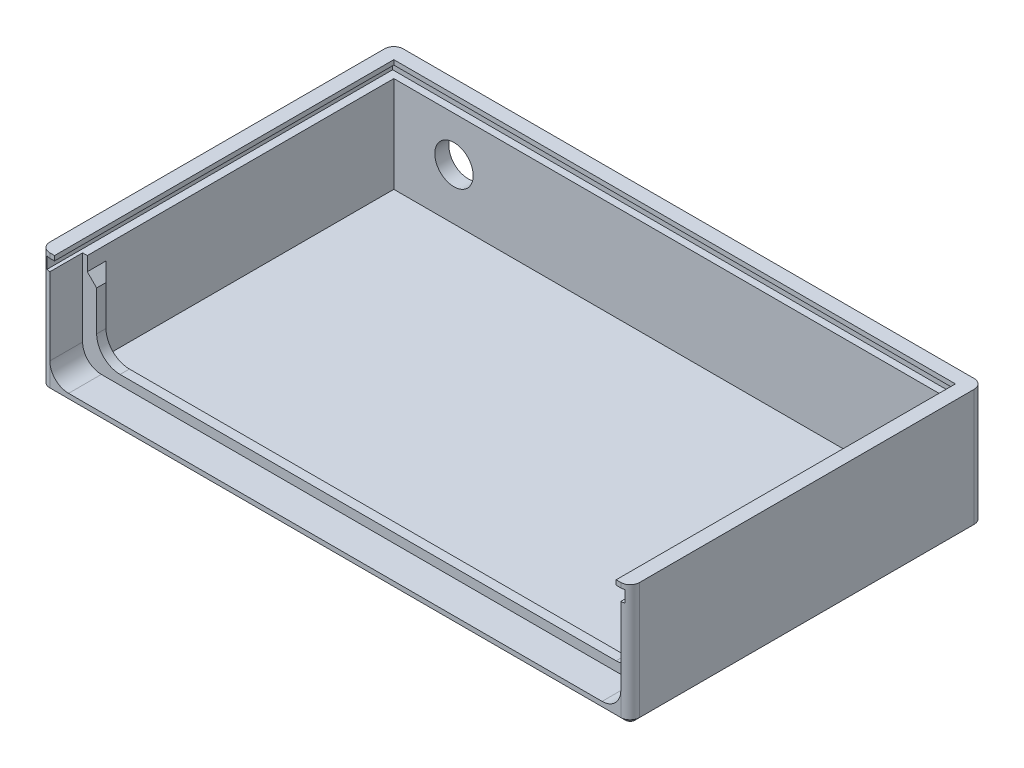
SolidWorks part; units mm, degrees
ref_plane "Plan de face" through (0, 0, 0) normal (0, 0, 1) x (1, 0, 0)
ref_plane "Plan de dessus" through (0, 0, 0) normal (0, 1, 0) x (1, 0, 0)
ref_plane "Plan de droite" through (0, 0, 0) normal (1, 0, 0) x (0, 0, -1)
sketch "Esquisse1" plane through (0, 0, 0) normal (0, 1, 0) x (1, 0, 0)
  line L1 (-63, -37.75) -> (63, -37.75)
  line L2 (-63, -37.75) -> (-63, 37.75)
  line L3 (-63, 37.75) -> (63, 37.75)
  line L4 (63, -37.75) -> (63, 37.75)
  line L5 (-63, -37.75) -> (63, 37.75) construction
  line L6 (-63, 37.75) -> (63, -37.75) construction
  point P0 (0, 0)
  dimension "D1" = 75.5
  dimension "D2" = 126
extrude "Boss.-Extru.1" add sketch "Esquisse1" along normal blind 2
sketch "Esquisse2" plane through (0, 2, 0) normal (0, 1, 0) x (1, 0, 0)
  line L0 (-63, -37.75) -> (-63, 37.75)
  line L1 (63, 37.75) -> (-63, 37.75) construction
  line L2 (-63, 37.75) -> (63, 37.75)
  line L3 (63, 37.75) -> (63, -37.75)
  line L4 (63, -37.75) -> (60, -37.75)
  line L5 (-63, -37.75) -> (63, -37.75) construction
  line L6 (60, -37.75) -> (60, 34.75)
  line L7 (60, 34.75) -> (-60, 34.75)
  line L8 (-60, 34.75) -> (-60, -37.75)
  line L9 (-60, -37.75) -> (-63, -37.75)
  line L10 (0, 34.75) -> (0, 37.75) construction
  dimension "D1" = 3
extrude "Boss.-Extru.2" add sketch "Esquisse2" along normal blind 24
ref_plane "Plan1" through (0, 25, 0) normal (0, 1, 0) x (1, 0, 0)
sketch "Esquisse3" plane through (0, 25, 0) normal (0, 1, 0) x (1, 0, 0)
  line L0 (60, -37.75) -> (63, -37.75) construction
  line L1 (-61.75, 36.25) -> (61.75, 36.25)
  line L2 (-61.75, 36.25) -> (-61.75, -37.75)
  line L3 (-61.75, -37.75) -> (61.75, -37.75)
  line L4 (61.75, 36.25) -> (61.75, -37.75)
  line L5 (-60, 34.75) -> (60, 34.75) construction
  line L6 (0, 0) -> (0, -37.75) construction
  dimension "D1" = 1.5
  dimension "D2" = 123.5
extrude "Enlèv. mat.-Extru.1" cut sketch "Esquisse3" against normal blind 2.5
sketch "Esquisse4" plane through (0, 0, 37.75) normal (0, 0, 1) x (1, 0, 0)
  line L0 (-60, 2) -> (-60, 17.5)
  line L1 (-60, 22.5) -> (-60, 2) construction
  line L2 (-60, 17.5) -> (-58, 17.5)
  line L3 (-58, 17.5) -> (-58, 9)
  line L4 (-53, 4) -> (0, 4)
  line L5 (0, 4) -> (0, 2)
  line L6 (-60, 2) -> (60, 2) construction
  line L7 (0, 2) -> (-60, 2)
  line L9 (61.75, 22.5) -> (-61.75, 22.5) construction
  arc A0 (-58, 9) -> (-53, 4) centre (-53, 9) ccw
  point P8 (-5.163, 9.9708)
  dimension "D1" = 5
  dimension "D2" = 2
  dimension "D3" = 5
extrude "Boss.-Extru.3" add sketch "Esquisse4" against normal blind 2 from offset 7 offset against normal yes
sketch "Esquisse5" plane through (0, 0, 37.75) normal (0, 0, 1) x (1, 0, 0)
  line L0 (-61.75, 22.5) -> (-60, 22.5) construction
  line L1 (-60, 2) -> (-61, 2)
  line L2 (-60, 2) -> (-60, 22.5)
  line L3 (-60, 22.5) -> (-61, 22.5)
  line L4 (-61, 2) -> (-61, 22.5)
  dimension "D1" = 1
extrude "Enlèv. mat.-Extru.2" cut sketch "Esquisse5" against normal up to surface (7 mm away) up to face at (-41.4336, 7.8521, 30.75)
draft "Dépouille1" type of draft neutral plane draft angle 45 faces to draft 1 face at (-59, 17.5, 29.75) neutral plane through (-58, 17.5, 28.75) neutral plane normal (1, 0, 0) parameters "D1"=45
mirror "Symétrie1" about plane through (0, 0, 0) normal (1, 0, 0) of "Dépouille1", "Boss.-Extru.3", "Enlèv. mat.-Extru.2"
sketch "Esquisse6" plane through (0, 0, -37.75) normal (0, 0, -1) x (-1, 0, 0)
  line L0 (-63, 0) -> (63, 0) construction
  circle A0 centre (47.15, 13) radius 4.1
  dimension "D1" = 8.2
  dimension "D2" = 47.15
  dimension "D3" = 13
extrude "Enlèv. mat.-Extru.3" cut sketch "Esquisse6" against normal up to next
fillet "Congé1" radius 4 2 edges at (61, 2, 34.25) (-61, 2, 34.25)
fillet "Congé2" radius 2 4 edges at (-63, 13, -37.75) (-63, 13, 37.75) (63, 13, 37.75) (63, 13, -37.75)
chamfer "Chanfrein1" distance 1 angle 45 8 edges at (0, 0, -37.75) (-63, 0, 0) (0, 0, 37.75) (63, 0, 0) (-62.4142, 0, 37.1642) (62.4142, 0, 37.1642) (62.4142, 0, -37.1642) (-62.4142, 0, -37.1642)
sketch "Esquisse7" plane through (0, 0, -37.75) normal (0, 0, -1) x (-1, 0, 0)
  line L0 (-20.85, 17.1) -> (39.15, 17.1) construction
  circle A0 centre (47.15, 13) radius 4.1 construction
  text T0 "<b>5V DC IN</b>" font "Century Gothic" height 8
  dimension "D1" = 8
  dimension "D2" = 60
extrude "Enlèv. mat.-Extru.4" cut sketch "Esquisse7" against normal blind 0.5
chamfer "Chanfrein2" distance 2 angle 45 3 edges at (60, 10.75, 28.75) (-60, 10.75, 28.75) (0, 2, 28.75)
